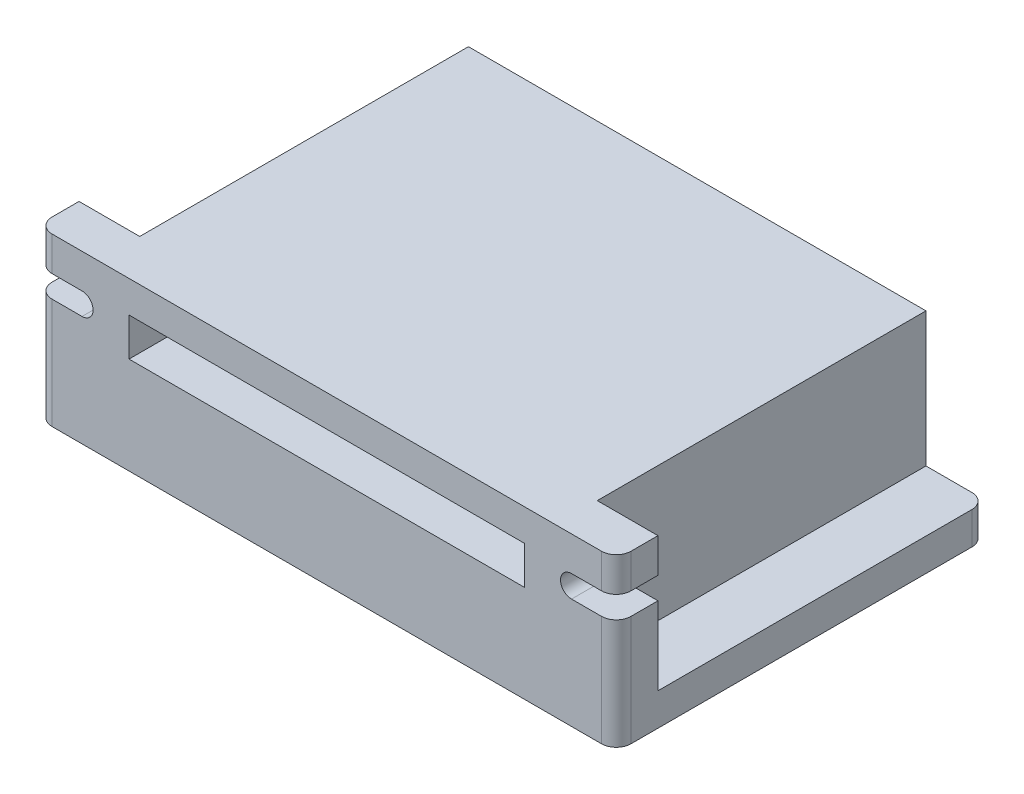
SolidWorks part; units mm, degrees
ref_plane "Front Plane" through (0, 0, 0) normal (0, 0, 1) x (1, 0, 0)
ref_plane "Top Plane" through (0, 0, 0) normal (0, 1, 0) x (1, 0, 0)
ref_plane "Right Plane" through (0, 0, 0) normal (1, 0, 0) x (0, 0, -1)
sketch "Sketch1" plane through (0, 0, 0) normal (0, 1, 0) x (1, 0, 0)
  line L1 (-56, -37.75) -> (56, -37.75)
  line L2 (-59, -34.75) -> (-59, 34.75)
  line L3 (-56, 37.75) -> (56, 37.75)
  line L4 (59, -34.75) -> (59, 34.75)
  line L5 (-59, -37.75) -> (59, 37.75) construction
  line L6 (-59, 37.75) -> (59, -37.75) construction
  arc A0 (-59, 34.75) -> (-56, 37.75) centre (-56, 34.75) cw
  arc A1 (56, 37.75) -> (59, 34.75) centre (56, 34.75) cw
  arc A2 (59, -34.75) -> (56, -37.75) centre (56, -34.75) cw
  arc A3 (-56, -37.75) -> (-59, -34.75) centre (-56, -34.75) cw
  point P0 (0, 0)
  dimension "D3" = 3
  dimension "D1" = 75.5
  dimension "D2" = 118
extrude "Boss-Extrude1" add sketch "Sketch1" along normal blind 34
sketch "Sketch2" plane through (0, 0, 37.75) normal (0, 0, 1) x (1, 0, 0)
  line L0 (-72.0827, 24.75) -> (-49.8883, 24.75) construction
  line L2 (-72.0827, 27) -> (-49.8883, 27)
  line L3 (-72.0827, 22.5) -> (-49.8883, 22.5)
  line L6 (-56, 34) -> (56, 34) construction
  arc A0 (-72.0827, 27) -> (-72.0827, 22.5) centre (-72.0827, 24.75) ccw
  arc A1 (-49.8883, 22.5) -> (-49.8883, 27) centre (-49.8883, 24.75) ccw
  point P4 (-60.9855, 24.75)
  dimension "D1" = 9.25
  dimension "D2" = 4.5
extrude "Cut-Extrude1" cut sketch "Sketch2" against normal blind 34
ref_point "Point1"
ref_axis "Axis1" through (0, 34, 0) along (0, 1, 0)
ref_plane "Plane1" through (0, 0, 0) normal (1, 0, 0) x (0, 1, 0)
mirror "Mirror1" about plane through (0, 0, 0) normal (1, 0, 0) of "Cut-Extrude1"
sketch "Sketch3" plane through (0, 0, -37.75) normal (0, 0, -1) x (-1, 0, 0)
  line L12 (-66.0825, 6.6158) -> (-46.6299, 6.6158)
  line L13 (-46.6299, 6.6158) -> (-46.6299, 40.7374)
  line L14 (-46.6299, 40.7374) -> (-66.0825, 40.7374)
  line L15 (-66.0825, 40.7374) -> (-66.0825, 6.6158)
extrude "Cut-Extrude2" cut sketch "Sketch3" against normal blind 67
mirror "Mirror2" about plane through (0, 0, 0) normal (1, 0, 0) of "Cut-Extrude2"
sketch "Sketch4" plane through (0, 0, 37.75) normal (0, 0, 1) x (1, 0, 0)
  line L1 (40.3098, 27.539) -> (-40.3098, 27.539)
  line L2 (40.3098, 27.539) -> (40.3098, 19.7633)
  line L3 (40.3098, 19.7633) -> (-40.3098, 19.7633)
  line L4 (-40.3098, 27.539) -> (-40.3098, 19.7633)
  line L5 (40.3098, 27.539) -> (-40.3098, 19.7633) construction
  line L6 (40.3098, 19.7633) -> (-40.3098, 27.539) construction
  point P0 (0, 23.6512)
extrude "Cut-Extrude3" cut sketch "Sketch4" against normal blind 10
